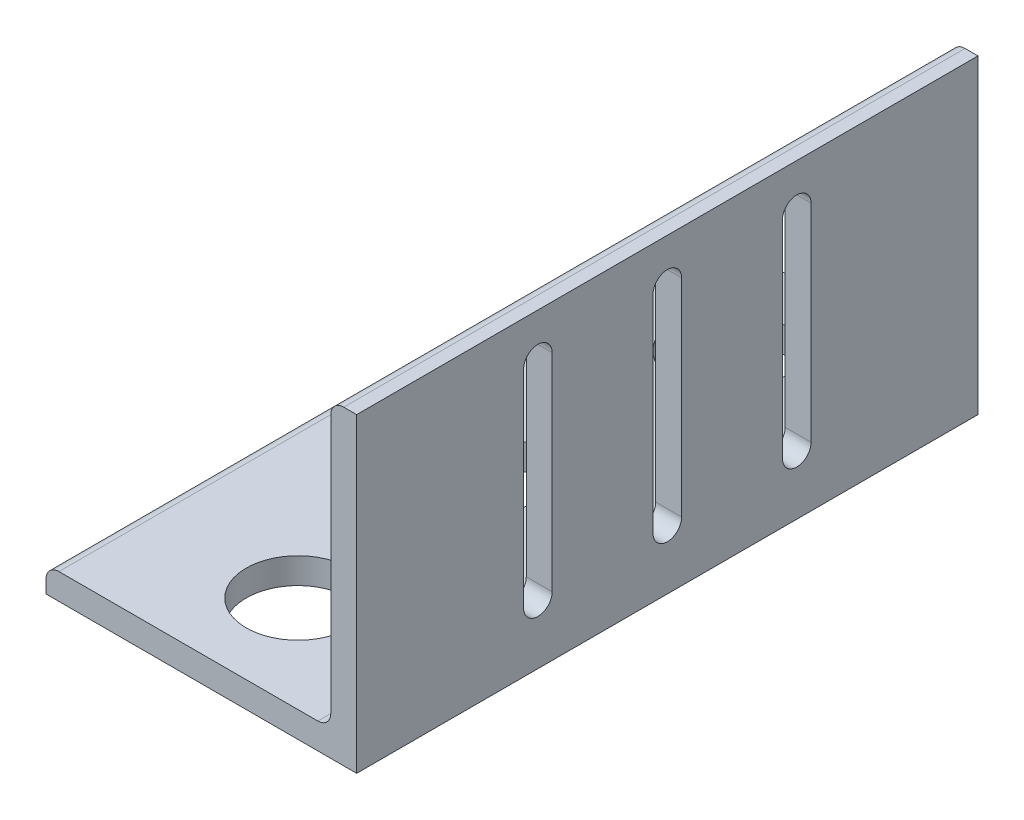
SolidWorks part; units mm, degrees
ref_plane "Front Plane" through (0, 0, 0) normal (0, 0, 1) x (1, 0, 0)
ref_plane "Top Plane" through (0, 0, 0) normal (0, 1, 0) x (1, 0, 0)
ref_plane "Right Plane" through (0, 0, 0) normal (1, 0, 0) x (0, 0, -1)
sketch "Sketch2" plane through (0, 0, 0) normal (0, 0, 1) x (1, 0, 0)
  line L0 (-38.1, 0) -> (38.1, 0)
  line L1 (38.1, 0) -> (38.1, 76.2)
  line L2 (38.1, 76.2) -> (31.75, 76.2) construction
  line L3 (31.75, 73.025) -> (31.75, 9.525)
  line L4 (28.575, 6.35) -> (-34.925, 6.35)
  line L5 (-38.1, 0) -> (-38.1, 6.35) construction
  line L6 (34.925, 76.2) -> (38.1, 76.2)
  line L7 (-38.1, 3.175) -> (-38.1, 0)
  arc A0 (31.75, 73.025) -> (34.925, 76.2) centre (34.925, 73.025) cw
  arc A1 (-38.1, 3.175) -> (-34.925, 6.35) centre (-34.925, 3.175) cw
  arc A2 (31.75, 9.525) -> (28.575, 6.35) centre (28.575, 9.525) cw
  dimension "Vert" = 76.2
  dimension "Horz" = 76.2
  dimension "Thickness" = 6.35
extrude "Boss-Extrude1" add sketch "Sketch2" along normal mid plane 152.4
ref_plane "Contact Plane 1" through (0, 6.35, 0) normal (0, 1, 0) x (1, 0, 0)
ref_plane "Contact Plane 2" through (31.75, 0, 0) normal (-1, 0, 0) x (0, 0, 1)
sketch "Sketch3" plane through (38.1, 0, 0) normal (1, 0, 0) x (0, 0, -1)
  line L0 (-31.75, 65.4) -> (-31.75, 14.6) construction
  line L1 (-28.25, 65.4) -> (-28.25, 14.6)
  line L2 (-35.25, 65.4) -> (-35.25, 14.6)
  line L3 (0, 0) -> (0, 76.2) construction
  line L4 (-76.2, 0) -> (76.2, 0) construction
  line L5 (-76.2, 76.2) -> (76.2, 76.2) construction
  line L6 (31.75, 65.4) -> (31.75, 14.6) construction
  line L7 (28.25, 65.4) -> (28.25, 14.6)
  line L8 (35.25, 65.4) -> (35.25, 14.6)
  line L9 (0, 65.4) -> (0, 14.6) construction
  line L10 (3.5, 65.4) -> (3.5, 14.6)
  line L11 (-3.5, 65.4) -> (-3.5, 14.6)
  arc A0 (-28.25, 65.4) -> (-35.25, 65.4) centre (-31.75, 65.4) ccw
  arc A1 (-35.25, 14.6) -> (-28.25, 14.6) centre (-31.75, 14.6) ccw
  arc A2 (28.25, 65.4) -> (35.25, 65.4) centre (31.75, 65.4) cw
  arc A3 (35.25, 14.6) -> (28.25, 14.6) centre (31.75, 14.6) cw
  arc A4 (3.5, 65.4) -> (-3.5, 65.4) centre (0, 65.4) ccw
  arc A5 (-3.5, 14.6) -> (3.5, 14.6) centre (0, 14.6) ccw
  point P2 (-31.75, 40)
  point P15 (31.75, 40)
  point P22 (0, 40)
  point P27 (0, 0)
  dimension "D1" = 3.5
  dimension "D3" = 31.75
  dimension "D5" = 3.5
  dimension "D2" = 50.8
  dimension "D4" = 40
  dimension "D6" = 50.8
extrude "Cut-Extrude1" cut sketch "Sketch3" against normal blind 10
sketch "Sketch4" plane through (0, 0, 0) normal (0, -1, 0) x (1, 0, 0)
  circle A2 centre (0, 0) radius 10
  circle A3 centre (0, 52.5) radius 12.7
  circle A4 centre (0, -52.5) radius 12.7
  dimension "D3" = 20
  dimension "D6" = 25.4
  dimension "D7" = 52.5
  dimension "D8" = 52.5
extrude "Cut-Extrude2" cut sketch "Sketch4" against normal blind 10
